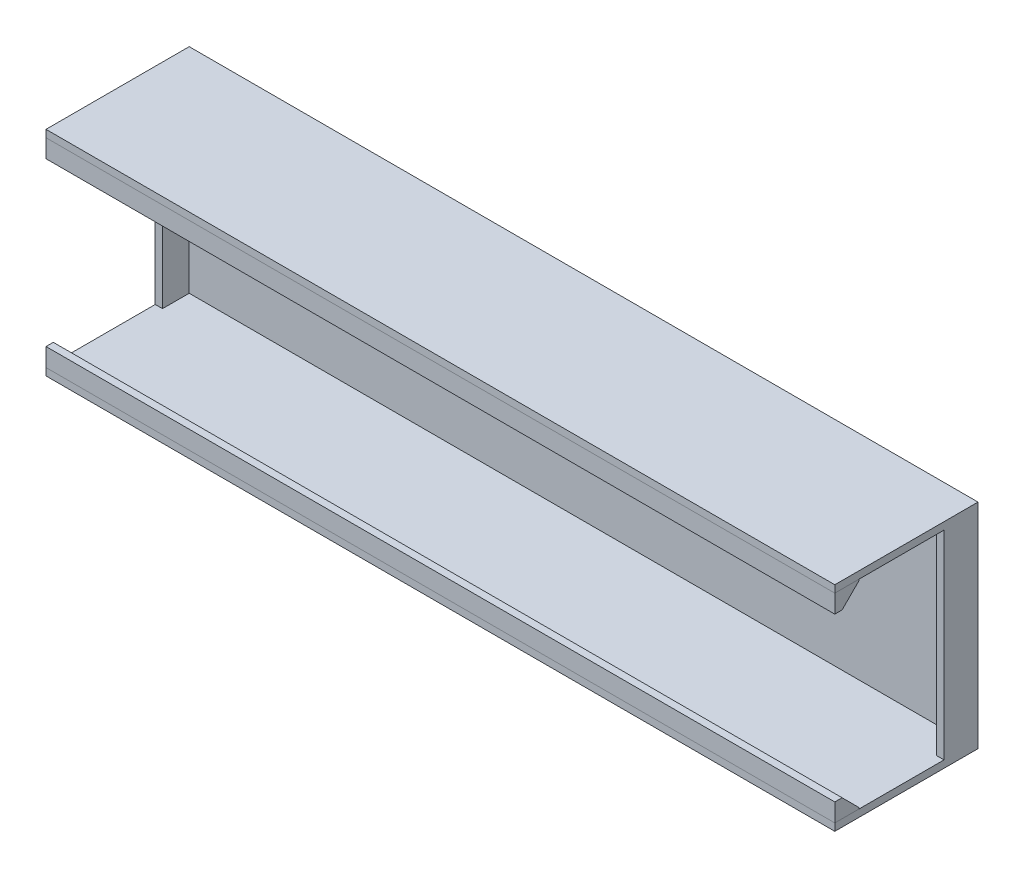
SolidWorks part; units mm, degrees
material "ABS"
ref_plane "Alzado" through (0, 0, 0) normal (0, 0, 1) x (1, 0, 0)
ref_plane "Planta" through (0, 0, 0) normal (0, 1, 0) x (1, 0, 0)
ref_plane "Vista lateral" through (0, 0, 0) normal (1, 0, 0) x (0, 0, -1)
sketch "Sketch1" plane through (0, 0, 0) normal (0, 0, 1) x (1, 0, 0)
  line L0 (0, 8.8) -> (0, -8.8) construction
  line L1 (-32.5, 8.8) -> (32.5, 8.8)
  line L2 (-32.5, 8.8) -> (-32.5, -8.8)
  line L3 (-32.5, -8.8) -> (32.5, -8.8)
  line L4 (32.5, 8.8) -> (32.5, -8.8)
  line L5 (-32.5, 8.8) -> (32.5, -8.8) construction
  line L6 (-32.5, -8.8) -> (32.5, 8.8) construction
  point P2 (0, 0)
  dimension "D1" = 17.6
  dimension "D2" = 65
extrude "Boss-Extrude1" add sketch "Sketch1" along normal blind 11.8
shell "Shell1" thickness 0.6 removed face at (0, 0, 11.8)
sketch "Sketch2" plane through (-32.5, 0, 0) normal (-1, 0, 0) x (0, 0, 1)
  line L0 (11.8, 8.8) -> (11.8, -8.8) construction
  line L1 (11.8, 8.2) -> (2.8, 8.2)
  line L2 (11.8, 8.2) -> (11.8, -8.2)
  line L3 (11.8, -8.2) -> (2.8, -8.2)
  line L4 (2.8, 8.2) -> (2.8, -8.2)
  point P6 (0, 0)
  point P7 (0, 0)
  point P8 (0, 0)
  dimension "D3" = 9
extrude "Cut-Extrude1" cut sketch "Sketch2" against normal through all
sketch "Sketch3" plane through (0, 0, 11.8) normal (0, 0, 1) x (1, 0, 0)
  line L0 (32.5, 8.2) -> (32.5, -8.2) construction
  line L1 (-32.5, 8.2) -> (32.5, 8.2)
  line L2 (-32.5, 8.2) -> (-32.5, 6.7)
  line L3 (-32.5, 6.7) -> (32.5, 6.7)
  line L4 (32.5, 8.2) -> (32.5, 6.7)
  line L5 (-32.5, 0) -> (32.5, 0) construction
  line L6 (-32.5, 8.2) -> (-32.5, -8.2) construction
  line L7 (-32.5, -6.7) -> (32.5, -6.7)
  line L8 (32.5, -8.2) -> (32.5, -6.7)
  line L9 (-32.5, -8.2) -> (32.5, -8.2)
  line L10 (-32.5, -8.2) -> (-32.5, -6.7)
  dimension "D1" = 1.5
extrude "Boss-Extrude2" add sketch "Sketch3" against normal blind 2 separate body
chamfer "Chamfer1" distance 1.4 angle 45 1 edges at (0, 6.7, 9.8)
chamfer "Chamfer2" distance 1.4 angle 45 1 edges at (0, -6.7, 9.8)
sketch "Sketch4" plane through (0, 0, 0) normal (0, 0, -1) x (-1, 0, 0)
  line L0 (0, 8.8) -> (0, -8.8) construction
  line L1 (-32.5, 8.8) -> (32.5, 8.8) construction
  line L2 (32.5, -8.8) -> (-32.5, -8.8) construction
  circle A0 centre (-10, 0) radius 2.75
  circle A1 centre (10, 0) radius 2.75
  dimension "D1" = 10
  dimension "D2" = 5.5
extrude "Cut-Extrude2" cut sketch "Sketch4" against normal blind 3
fillet "Fillet2" radius 2 2 edges at (12.75, 0, 0.6) (-7.25, 0, 0.6)
